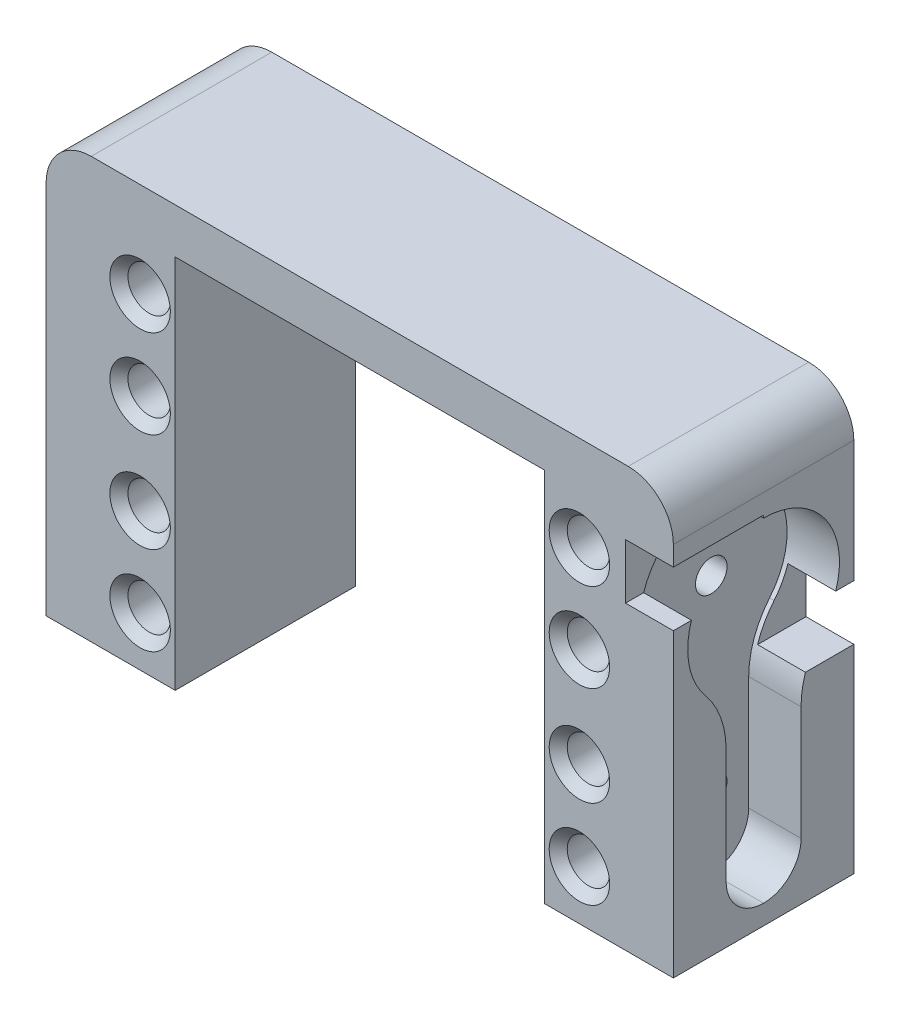
SolidWorks part; units mm, degrees
material "ABS"
ref_plane "Front Plane" through (0, 0, 0) normal (0, 0, 1) x (1, 0, 0)
ref_plane "Top Plane" through (0, 0, 0) normal (0, 1, 0) x (1, 0, 0)
ref_plane "Right Plane" through (0, 0, 0) normal (1, 0, 0) x (0, 0, -1)
sketch "Sketch1" plane through (0, 0, 0) normal (1, 0, 0) x (0, 0, -1)
  line L1 (-10, 10) -> (10, 10)
  line L2 (-10, 10) -> (-10, -10)
  line L3 (-10, -10) -> (10, -10)
  line L4 (10, 10) -> (10, -10)
  line L5 (-10, 10) -> (10, -10) construction
  line L6 (-10, -10) -> (10, 10) construction
  point P0 (0, 0)
  dimension "D1" = 20
  dimension "D2" = 20
extrude "Boss-Extrude1" add sketch "Sketch1" along normal blind 20
sketch "Sketch2" plane through (20, 0, 0) normal (1, 0, 0) x (0, 0, -1)
  line L1 (-10, 35) -> (10, 35)
  line L2 (-10, 35) -> (-10, -35)
  line L3 (-10, -35) -> (10, -35)
  line L4 (10, 35) -> (10, -35)
  line L5 (-10, 35) -> (10, -35) construction
  line L6 (-10, -35) -> (10, 35) construction
  point P0 (0, 0)
  dimension "D1" = 20
  dimension "D2" = 70
extrude "Boss-Extrude2" add sketch "Sketch2" along normal blind 10.3
sketch "Sketch4" plane through (30.3, 0, 0) normal (1, 0, 0) x (0, 0, -1)
  line L0 (0, 7.65) -> (0, 8.1702) construction
  line L1 (7.65, 7.65) -> (-7.65, 7.65) construction
  line L17 (4.15, -26.55) -> (-4.15, -26.55) construction
  line L18 (-7.65, 7.65) -> (7.65, 7.65) construction
  line L22 (-7.65, 7.65) -> (-7.65, -27.55) construction
  line L23 (-7.65, -27.55) -> (7.65, -27.55) construction
  line L24 (7.65, 7.65) -> (7.65, -27.55) construction
  line L25 (-7.65, 7.65) -> (7.65, -27.55) construction
  line L26 (-7.65, -27.55) -> (7.65, 7.65) construction
  line L27 (4.15, -26.55) -> (4.15, -28.55) construction
  line L28 (4.15, -28.55) -> (-4.15, -28.55) construction
  line L29 (-4.15, -26.55) -> (-4.15, -28.55) construction
  line L30 (4.15, -26.55) -> (-4.15, -28.55) construction
  line L31 (4.15, -28.55) -> (-4.15, -26.55) construction
  line L34 (4.15, -28.55) -> (-4.15, -28.55)
  line L35 (-4.15, -28.55) -> (-4.15, -7.3118)
  line L36 (4.15, -28.55) -> (4.15, -7.3118)
  arc A1 (4.15, -6.4265) -> (-4.15, -6.4265) centre (0, 0) ccw construction
  arc A2 (4.15, -7.3118) -> (-4.15, -7.3118) centre (0, 0) ccw
  point P1 (0, -27.55)
  point P7 (0, -13.75)
  point P10 (0, 7.65)
  point P14 (0, -9.95)
  dimension "D1" = 15.3
  dimension "D5" = 2
  dimension "D2" = 15.3
  dimension "D3" = 35.2
  dimension "D4" = 8.3
extrude "Cut-Extrude1" cut sketch "Sketch4" against normal blind 5.8
fillet "Fillet1" radius 4.15 2 edges at (27.4, -28.55, 4.15) (27.4, -28.55, -4.15)
fillet "Fillet2" radius 10 2 edges at (27.4, -7.3118, 4.15) (27.4, -7.3118, -4.15)
sketch "Sketch5" plane through (0, 0, 0) normal (-1, 0, 0) x (0, 0, 1)
  circle A0 centre (0, 0) radius 1.75
  dimension "D1" = 3.5
extrude "Cut-Extrude2" cut sketch "Sketch5" against normal through all
sketch "Sketch6" plane through (24.5, 0, 0) normal (1, 0, 0) x (0, 0, -1)
  line L0 (0, -19.35) -> (0, 0) construction
  line L1 (0, -25.65) -> (0, -23.15) construction
  line L2 (0, -23.15) -> (0, -21.85) construction
  line L3 (0, -21.85) -> (0, -19.35) construction
  line L5 (0, 0) -> (1.164, 0) construction
  line L6 (0, 0) -> (0, -9.35) construction
  line L7 (0, -9.35) -> (1.164, -9.35) construction
  line L8 (1.164, 0) -> (1.164, -9.35) construction
  line L9 (0, 0) -> (1.164, -9.35) construction
  line L10 (0, -9.35) -> (1.164, 0) construction
  circle A0 centre (0, -20.6) radius 1.75
  circle A1 centre (0, -9.35) radius 1.75 construction
  point P11 (0.582, -4.675)
  dimension "D5" = 3.5
  dimension "D6" = 9.35
  dimension "D7" = 3.5
  dimension "D1" = 19.35
  dimension "D2" = 2.5
  dimension "D3" = 1.3
  dimension "D4" = 2.5
extrude "Cut-Extrude3" cut sketch "Sketch6" against normal up to next
sketch "Sketch13" plane through (0, 0, 0) normal (-1, 0, 0) x (0, 0, 1)
  line L1 (-10, 10) -> (10, 10)
  line L2 (-10, 10) -> (-10, -10)
  line L3 (-10, -10) -> (10, -10)
  line L4 (10, 10) -> (10, -10)
extrude "Cut-Extrude9" cut sketch "Sketch13" against normal up to surface (20 mm away) up to face at (20, 22.5, 0)
sketch "Sketch29" plane through (30.3, 0, 0) normal (1, 0, 0) x (0, 0, -1)
  line L0 (0, 0) -> (0, 2.6) construction
  line L1 (15.1094, -8.7) -> (15.1094, -2.6)
  line L2 (0, 2.6) -> (-15.1094, 2.6)
  line L4 (0, 2.6) -> (0, 3.8)
  line L5 (0, 3.8) -> (0, 7.5)
  line L6 (0, 7.5) -> (0, 8.7)
  line L7 (0, 8.7) -> (-15.1094, 8.7)
  line L8 (-15.1094, 8.7) -> (-15.1094, 2.6)
  line L9 (0, -2.6) -> (15.1094, -2.6)
  line L10 (0, -2.6) -> (0, -3.8)
  line L11 (0, -3.8) -> (0, -7.5)
  line L12 (0, -7.5) -> (0, -8.7)
  line L13 (0, -8.7) -> (15.1094, -8.7)
  point P19 (0, 0)
  dimension "D1" = 2.6
  dimension "D2" = 1.2
  dimension "D3" = 3.7
  dimension "D4" = 1.2
  dimension "D5" = 2
extrude "Cut-Extrude18" cut sketch "Sketch29" against normal blind 5.3
sketch "Sketch32" plane through (30.3, 0, 0) normal (1, 0, 0) x (0, 0, -1)
  line L0 (0, -28.55) -> (0, -35.725) construction
  line L1 (10, -35) -> (10, -8.7) construction
  line L2 (-10, -35) -> (10, -35)
  line L3 (-10, -35) -> (-10, -35.725)
  line L4 (-10, -35.725) -> (10, -35.725)
  line L5 (10, -35) -> (10, -35.725)
  dimension "D1" = 7.175
extrude "Boss-Extrude3" add sketch "Sketch32" against normal up to surface (10.3 mm away) up to face at (20, 0, 0)
sketch "Sketch31" plane through (30.3, 0, 0) normal (1, 0, 0) x (0, 0, -1)
  line L2 (0, 8.7) -> (0, 15.875) construction
  line L3 (10, -2.6) -> (10, 35) construction
  line L4 (-10, 35) -> (10, 35)
  line L5 (-10, 35) -> (-10, 15.875)
  line L6 (-10, 15.875) -> (10, 15.875)
  line L7 (10, 35) -> (10, 15.875)
  dimension "D1" = 7.175
extrude "Cut-Extrude19" cut sketch "Sketch31" against normal through all
sketch "Sketch34" plane through (20, 0, 0) normal (-1, 0, 0) x (0, 0, 1)
  line L4 (10, -35.725) -> (10, 15.875)
  line L5 (10, 15.875) -> (-10, 15.875)
  line L6 (-10, 15.875) -> (-10, -35.725)
  line L7 (-10, -35.725) -> (10, -35.725)
  line L8 (10, -35.725) -> (10, 15.875)
  line L9 (10, 15.875) -> (-10, 15.875)
  line L10 (-10, 15.875) -> (-10, -35.725)
  line L11 (-10, -35.725) -> (10, -35.725)
  circle A0 centre (0, -20.6) radius 1.75 construction
  circle A1 centre (0, 0) radius 1.75 construction
  circle A2 centre (0, -20.6) radius 1.75
  circle A3 centre (0, 0) radius 1.75
  dimension "D1" = 0
extrude "Boss-Extrude5" add sketch "Sketch34" along normal blind 4
sketch "Sketch35" plane through (16, 0, 0) normal (-1, 0, 0) x (0, 0, 1)
  line L0 (10, -35.725) -> (10, 15.875) construction
  line L1 (-10, 15.875) -> (10, 15.875)
  line L2 (-10, 15.875) -> (-10, 10.875)
  line L3 (-10, 10.875) -> (10, 10.875)
  line L4 (10, 15.875) -> (10, 10.875)
  line L5 (0, 10.875) -> (0, -30.725) construction
  line L6 (-10, -35.725) -> (10, -35.725) construction
  line L7 (-10, -35.725) -> (-10, -30.725) construction
  line L8 (-10, -30.725) -> (10, -30.725) construction
  line L9 (10, -35.725) -> (10, -30.725) construction
  dimension "D1" = 41.6
extrude "Boss-Extrude6" add sketch "Sketch35" along normal blind 40.9
sketch "Sketch37" plane through (-24.9, 0, 0) normal (-1, 0, 0) x (0, 0, 1)
  line L1 (-10, 15.875) -> (10, 15.875)
  line L2 (-10, 15.875) -> (-10, -35.725)
  line L3 (-10, -35.725) -> (10, -35.725)
  line L4 (10, 15.875) -> (10, -35.725)
extrude "Boss-Extrude7" add sketch "Sketch37" along normal blind 14.3
sketch "Sketch38" plane through (0, 0, 10) normal (0, 0, 1) x (1, 0, 0)
  line L0 (-24.9, 10.875) -> (-24.9, -9.925) construction
  line L1 (-24.9, -9.925) -> (-24.9, -30.725) construction
  line L2 (-24.9, -35.725) -> (-24.9, 10.875) construction
  line L3 (-24.9, -9.925) -> (-39.2, -9.925) construction
  line L4 (-39.2, -35.725) -> (-39.2, 15.875) construction
  line L5 (-24.9, 0.475) -> (-28.79, 0.475) construction
  line L6 (-28.79, 0.475) -> (-28.79, 5.375) construction
  line L7 (-24.9, 10.875) -> (16, 10.875) construction
  line L8 (-4.45, 10.875) -> (-4.45, -35.725) construction
  line L9 (-24.9, -35.725) -> (-4.45, -35.725) construction
  circle A0 centre (-28.79, 5.375) radius 2.35
  circle A1 centre (-28.79, -4.425) radius 2.35
  circle A2 centre (-28.79, -25.225) radius 2.35
  circle A3 centre (-28.79, -15.425) radius 2.35
  circle A4 centre (19.89, 5.375) radius 2.35
  circle A5 centre (19.89, -4.425) radius 2.35
  circle A6 centre (19.89, -15.425) radius 2.35
  circle A7 centre (19.89, -25.225) radius 2.35
  dimension "D4" = 4.7
  dimension "D1" = 41.6
  dimension "D2" = 3.89
  dimension "D3" = 4.9
extrude "Cut-Extrude20" cut sketch "Sketch38" against normal blind 8
chamfer "Chamfer1" distance 1 angle 45 8 edges at (22.24, -25.225, 10) (17.54, -15.425, 10) (22.24, -4.425, 10) (17.54, 5.375, 10) (-26.44, 5.375, 10) (-26.44, -15.425, 10) (-31.14, -25.225, 10) (-31.14, -4.425, 10)
sketch "Sketch39" plane through (0, 0, 10) normal (0, 0, 1) x (1, 0, 0)
  line L0 (30.3, 2.6) -> (30.3, -35.725) construction
  line L1 (-39.2, -35.725) -> (30.3, -35.725)
  line L2 (-39.2, -35.725) -> (-39.2, -30.725)
  line L3 (-39.2, -30.725) -> (30.3, -30.725)
  line L4 (30.3, -35.725) -> (30.3, -30.725)
  dimension "D1" = 5
extrude "Cut-Extrude21" cut sketch "Sketch39" against normal through all
sketch "Sketch40" plane through (0, -30.725, 0) normal (0, -1, 0) x (1, 0, 0)
  line L0 (-32.05, 10) -> (-32.05, -10) construction
  line L1 (-24.9, 10) -> (-39.2, 10) construction
  line L2 (-24.9, -10) -> (-39.2, -10) construction
  line L4 (23.15, 10) -> (23.15, -10) construction
  line L5 (30.3, 10) -> (16, 10) construction
  line L6 (30.3, -10) -> (16, -10) construction
  line L7 (23.15, 0) -> (-32.05, 0) construction
  line L8 (-4.45, 0) -> (-4.45, -10) construction
  line L9 (-4.45, -10) -> (-32.05, -10) construction
  line L10 (-24.9, 10) -> (-24.9, -10) construction
  circle A2 centre (-28.79, 0) radius 2.35
  circle A3 centre (19.89, 0) radius 2.35
  dimension "D1" = 3.89
  dimension "D2" = 4.7
extrude "Cut-Extrude22" cut sketch "Sketch40" against normal blind 8
chamfer "Chamfer2" distance 1 angle 45 2 edges at (17.54, -30.725, 0) (-26.44, -30.725, 0)
fillet "Fillet3" radius 5 2 edges at (30.3, 15.875, 0) (-39.2, 15.875, 0)
